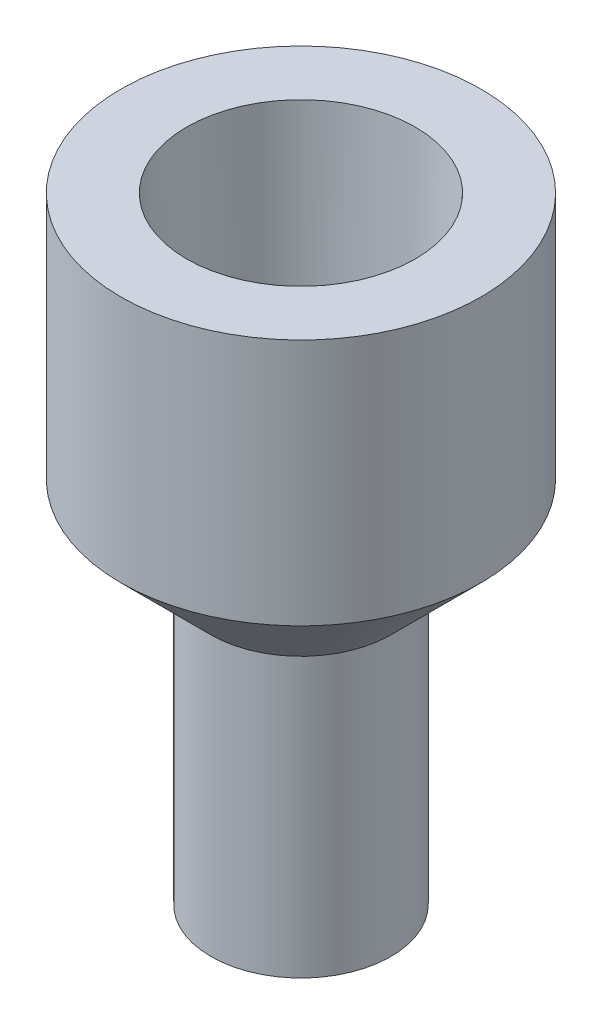
SolidWorks part; units mm, degrees
ref_plane "Front Plane" through (0, 0, 0) normal (0, 0, 1) x (1, 0, 0)
ref_plane "Top Plane" through (0, 0, 0) normal (0, 1, 0) x (1, 0, 0)
ref_plane "Right Plane" through (0, 0, 0) normal (1, 0, 0) x (0, 0, -1)
sketch "Sketch1" plane through (0, 0, 0) normal (0, 1, 0) x (1, 0, 0)
  circle A0 centre (0, 0) radius 5.08
  dimension "D1" = 10.16
extrude "Boss-Extrude1" add sketch "Sketch1" along normal blind 20.8
sketch "Sketch2" plane through (0, 20.8, 0) normal (0, 1, 0) x (1, 0, 0)
  circle A0 centre (0, 0) radius 10.16
  dimension "D1" = 20.32
extrude "Boss-Extrude2" add sketch "Sketch2" along normal blind 13.97
sketch "Sketch3" plane through (0, 34.77, 0) normal (0, 1, 0) x (1, 0, 0)
  circle A0 centre (0, 0) radius 6.45
  dimension "D1" = 12.9
ref_plane "Plane1" through (0, 23.34, 0) normal (0, -1, 0) x (-1, 0, 0)
sketch "Sketch4" plane through (0, 23.34, 0) normal (0, -1, 0) x (-1, 0, 0)
  circle A0 centre (0, 0) radius 6.0522
  dimension "D1" = 12.1043
loft "Cut-Loft1" cut profiles "Sketch4", "Sketch3" connector at (-5.8446, 23.34, -1.5713) connector at (-5.9621, 34.77, -2.4608)
chamfer "Chamfer1" distance 5.08 angle 45 1 edges at (0, 20.8, 5.08)
sketch "Sketch5" plane through (0, 0, 0) normal (0, -1, 0) x (1, 0, 0)
  circle A0 centre (0, 0) radius 2.525
  dimension "D1" = 5.05
ref_plane "Plane2" through (0, 18.26, 0) normal (0, -1, 0) x (-1, 0, 0)
sketch "Sketch6" plane through (0, 18.26, 0) normal (0, -1, 0) x (-1, 0, 0)
  circle A0 centre (0, 0) radius 2.325
  dimension "D1" = 4.65
loft "Cut-Loft2" cut profiles "Sketch6", "Sketch5" connector at (-2.1982, 18.26, -0.7573) connector at (-2.2278, 0, -1.1885)
equation "\"D1@Sketch3\"=0.50in + 0.2mm"
